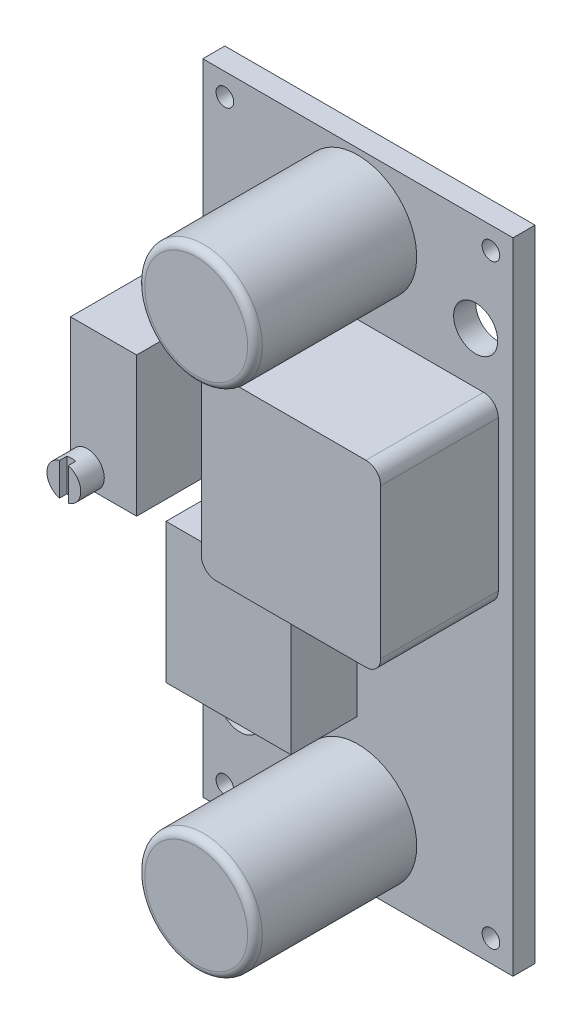
SolidWorks part; units mm, degrees
note: The reader was unsure of these and kept them because the rebuilt part matched: shared geometry of "Эскиз7<3>", "Эскиз7<4>", "Эскиз4<3><3>".
material "AISI 1020 Steel, Cold Rolled"
ref_plane "Спереди" through (0, 0, 0) normal (0, 0, 1) x (1, 0, 0)
ref_plane "Сверху" through (0, 0, 0) normal (0, 1, 0) x (1, 0, 0)
ref_plane "Справа" through (0, 0, 0) normal (1, 0, 0) x (0, 0, -1)
sketch "Эскиз1" plane through (0, 0, 0) normal (0, 0, 1) x (1, 0, 0)
  line L1 (-10.55, -21.75) -> (10.55, -21.75)
  line L2 (-10.55, -21.75) -> (-10.55, 21.75)
  line L3 (-10.55, 21.75) -> (10.55, 21.75)
  line L4 (10.55, -21.75) -> (10.55, 21.75)
  line L5 (0, 21.75) -> (0, -21.75) construction
  line L6 (-10.55, 0) -> (10.55, 0) construction
  point P0 (0, 0)
  dimension "D1" = 21.1
  dimension "D2" = 43.5
extrude "Бобышка-Вытянуть1" add sketch "Эскиз1" along normal blind 1.5
sketch "Эскиз6" plane through (0, 0, 1.5) normal (0, 0, 1) x (1, 0, 0)
  line L0 (10.55, -21.75) -> (10.55, 21.75) construction
  line L1 (-10.55, 21.75) -> (-10.55, -21.75) construction
  line L2 (10.55, 21.75) -> (-10.55, 21.75) construction
  line L3 (-10.55, -21.75) -> (10.55, -21.75) construction
  line L4 (0, -0.825) -> (0, 0.825) construction
  line L5 (0.825, 0) -> (-0.825, 0) construction
  circle A0 centre (8.01, 15.15) radius 1.5
  circle A1 centre (-8.01, -15.15) radius 1.5
  circle A2 centre (9.05, 20.25) radius 0.6
  circle A3 centre (-9.05, 20.25) radius 0.6
  circle A4 centre (9.05, -20.25) radius 0.6
  circle A5 centre (-9.05, -20.25) radius 0.6
  dimension "D1" = 3
  dimension "D6" = 1.2
  dimension "D2" = 2.54
  dimension "D3" = 2.54
  dimension "D4" = 6.6
  dimension "D5" = 6.6
  dimension "D7" = 1.5
  dimension "D8" = 1.5
extrude "Вырез-Вытянуть2" cut sketch "Эскиз6" against normal up to surface (1.5 mm away) up to face at (0, 0, 0)
sketch "Эскиз7" plane through (0, 0, 1.5) normal (0, 0, 1) x (1, 0, 0)
  line L0 (10.55, 21.75) -> (-10.55, 21.75) construction
  line L1 (0.825, 0) -> (-0.825, 0) construction
  line L2 (-10.55, 21.75) -> (-10.55, -21.75) construction
  line L3 (-8.55, -2.25) -> (-0.05, -2.25)
  line L4 (-8.55, -2.25) -> (-8.55, -11.75)
  line L5 (-8.55, -11.75) -> (-0.05, -11.75)
  line L6 (-0.05, -2.25) -> (-0.05, -11.75)
  line L7 (-10.55, -21.75) -> (10.55, -21.75) construction
  line L8 (10.55, -21.75) -> (10.55, 21.75) construction
  line L9 (8.55, 11.65) -> (-1.65, 11.65)
  line L10 (9.55, 10.65) -> (9.55, 0.45)
  line L11 (8.55, -0.55) -> (-1.65, -0.55)
  line L12 (-2.65, 10.65) -> (-2.65, 0.45)
  circle A0 centre (0, 17.35) radius 4
  circle A1 centre (0, -17.35) radius 4
  arc A2 (-1.65, 11.65) -> (-2.65, 10.65) centre (-1.65, 10.65) ccw
  arc A3 (-2.65, 0.45) -> (-1.65, -0.55) centre (-1.65, 0.45) ccw
  arc A4 (9.55, 0.45) -> (8.55, -0.55) centre (8.55, 0.45) cw
  arc A5 (8.55, 11.65) -> (9.55, 10.65) centre (8.55, 10.65) cw
  dimension "D1" = 8
  dimension "D7" = 1
  dimension "D2" = 4.4
  dimension "D3" = 8.5
  dimension "D4" = 9.5
  dimension "D5" = 2
  dimension "D6" = 10
  dimension "D8" = 12.2
  dimension "D9" = 10.1
  dimension "D10" = 1
extrude "Бобышка-Вытянуть9" add sketch "Эскиз7" along normal blind 11 contours A0 | A1
extrude "Бобышка-Вытянуть10" add sketch "Эскиз7<3>" along normal blind 8 contours A5 L9 A2 L12 A3 L11 A4 L10
sketch "Эскиз7<3>" plane through (0, 0, 1.5) normal (0, 0, 1) x (1, 0, 0) same geometry as "Эскиз7"
extrude "Бобышка-Вытянуть11" add sketch "Эскиз7<4>" along normal blind 4.5 contours L6 L3 L4 L5
sketch "Эскиз7<4>" plane through (0, 0, 1.5) normal (0, 0, 1) x (1, 0, 0) same geometry as "Эскиз7"
fillet "Скругление1" radius 0.5 2 edges at (4, -17.35, 12.5) (4, 17.35, 12.5)
sketch "Эскиз4<3>" plane through (5.4755, 30.6343, 1.5) normal (0, 0, 1) x (1, 0, 0)
  line L1 (-15.0255, -18.5843) -> (-10.5255, -18.5843)
  line L2 (-15.0255, -18.5843) -> (-15.0255, -28.0843)
  line L3 (-15.0255, -28.0843) -> (-10.5255, -28.0843)
  line L4 (-10.5255, -18.5843) -> (-10.5255, -28.0843)
  line L10 (-16.0255, -8.8843) -> (-16.0255, -52.3843) construction
  line L16 (-16.0255, -52.3843) -> (5.0745, -52.3843) construction
  circle A0 centre (-13.8755, -26.9343) radius 1.15
  dimension "D4" = 2.3
  dimension "D1" = 4.5
  dimension "D2" = 9.5
  dimension "D3" = 24.3
  dimension "D5" = 1
extrude "Бобышка-Вытянуть7" add sketch "Эскиз4<3>" along normal blind 10 separate body
extrude "Бобышка-Вытянуть8" add sketch "Эскиз4<3><3>" along normal blind 1.6 from surface at 10
sketch "Эскиз4<3><3>" plane through (5.4755, 30.6343, 1.5) normal (0, 0, 1) x (1, 0, 0) same geometry as "Эскиз4<3>"
sketch "Эскиз5" plane through (6.95, -7.75, 13.1) normal (0, 0, 1) x (1, 0, 0)
  line L0 (-15.65, 11.45) -> (-15.05, 11.45) construction
  line L1 (-15.65, 12.95) -> (-15.05, 12.95)
  line L2 (-15.65, 12.95) -> (-15.65, 9.95)
  line L3 (-15.65, 9.95) -> (-15.05, 9.95)
  line L4 (-15.05, 12.95) -> (-15.05, 9.95)
  circle A0 centre (-15.35, 11.45) radius 1.15 construction
  point P6 (-15.35, 11.45)
  dimension "D1" = 0.6
  dimension "D2" = 3
extrude "Вырез-Вытянуть1" cut sketch "Эскиз5" against normal blind 0.5
other "Подстроечный резистор<1>"
equation "\"D8@Эскиз6\"=\"D7@Эскиз6\""
